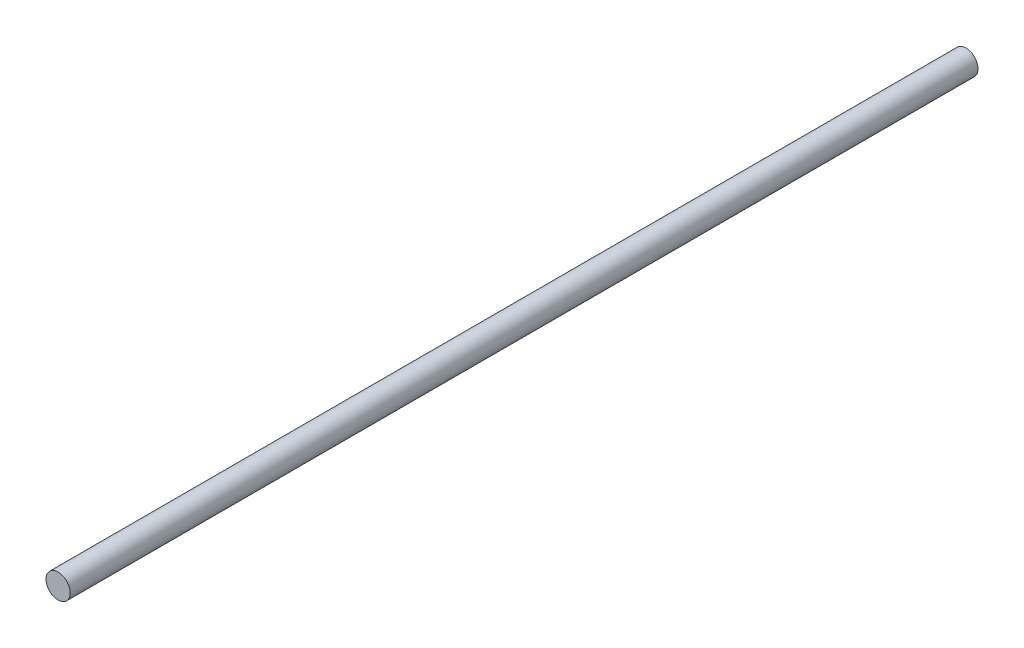
SolidWorks part; units mm, degrees
ref_plane "Front Plane" through (0, 0, 0) normal (0, 0, 1) x (1, 0, 0)
ref_plane "Top Plane" through (0, 0, 0) normal (0, 1, 0) x (1, 0, 0)
ref_plane "Right Plane" through (0, 0, 0) normal (1, 0, 0) x (0, 0, -1)
sketch "Sketch1" plane through (0, 0, 0) normal (0, 0, 1) x (1, 0, 0)
  circle A0 centre (0, 0) radius 2
  dimension "D1" = 4
extrude "Boss-Extrude1" add sketch "Sketch1" along normal blind 150
